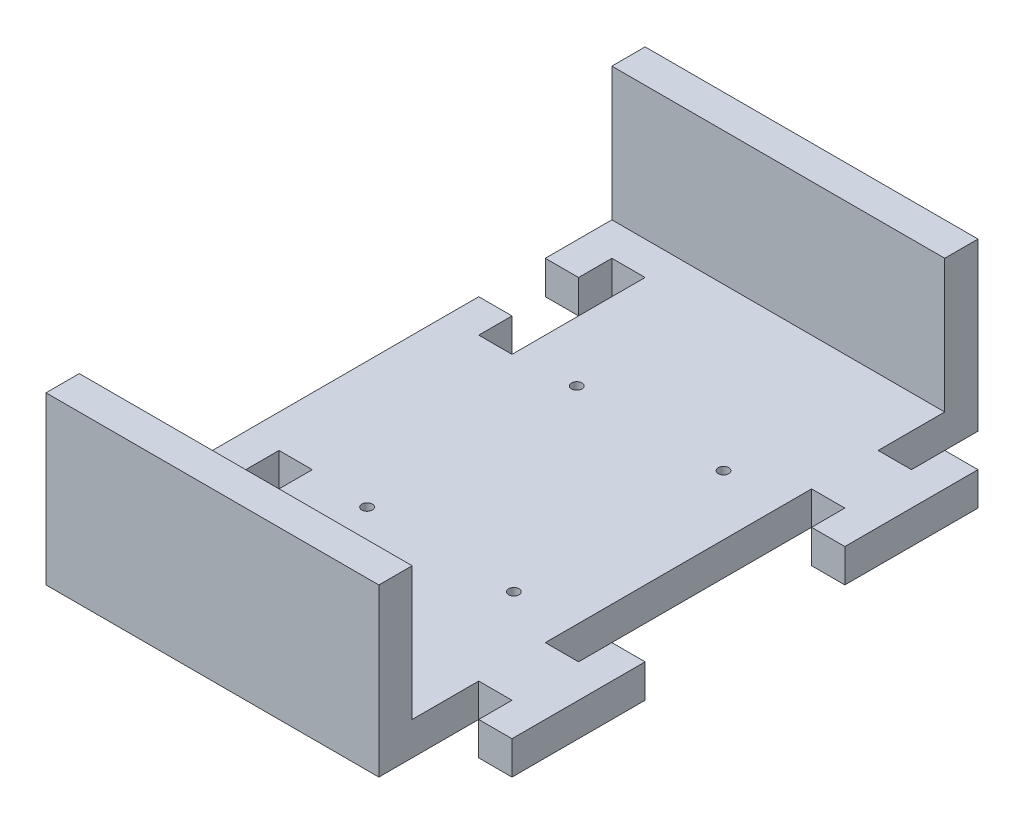
SolidWorks part; units mm, degrees
ref_plane "Front Plane" through (0, 0, 0) normal (0, 0, 1) x (1, 0, 0)
ref_plane "Top Plane" through (0, 0, 0) normal (0, 1, 0) x (1, 0, 0)
ref_plane "Right Plane" through (0, 0, 0) normal (1, 0, 0) x (0, 0, -1)
sketch "Sketch1" plane through (0, 0, 0) normal (0, 1, 0) x (1, 0, 0)
  line L1 (-38.1, -57.15) -> (25.4, -57.15)
  line L2 (-38.1, -57.15) -> (-38.1, 57.15)
  line L3 (-38.1, 57.15) -> (25.4, 57.15)
  line L4 (25.4, -57.15) -> (25.4, 57.15)
  line L5 (-38.1, -57.15) -> (25.4, 57.15) construction
  line L6 (-38.1, 57.15) -> (25.4, -57.15) construction
  point P0 (-6.35, 0)
  point P6 (0, 0)
  dimension "D1" = 63.5
  dimension "D2" = 114.3
  dimension "D3" = 6.35
extrude "Boss-Extrude1" add sketch "Sketch1" along normal blind 6.35
sketch "Sketch2" plane through (0, 6.35, 0) normal (0, 1, 0) x (1, 0, 0)
  line L1 (-14, -20) -> (14, -20) construction
  line L2 (-14, -20) -> (-14, 20) construction
  line L3 (-14, 20) -> (14, 20) construction
  line L4 (14, -20) -> (14, 20) construction
  line L5 (-14, -20) -> (14, 20) construction
  line L6 (-14, 20) -> (14, -20) construction
  circle A0 centre (-14, 20) radius 1
  circle A1 centre (14, 20) radius 1
  circle A2 centre (14, -20) radius 1
  circle A3 centre (-14, -20) radius 1
  point P0 (0, 0)
  dimension "D3" = 2
  dimension "D1" = 28
  dimension "D2" = 40
extrude "Cut-Extrude1" cut sketch "Sketch2" against normal through all
sketch "Sketch3" plane through (0, 6.35, 0) normal (0, 1, 0) x (1, 0, 0)
  line L0 (25.4, -57.15) -> (25.4, 57.15) construction
  line L1 (-38.1, 57.15) -> (25.4, 57.15)
  line L2 (-38.1, 57.15) -> (-38.1, 50.8)
  line L3 (-38.1, 50.8) -> (25.4, 50.8)
  line L4 (25.4, 57.15) -> (25.4, 50.8)
  line L6 (-38.1, -57.15) -> (25.4, -57.15)
  line L7 (-38.1, -57.15) -> (-38.1, -50.8)
  line L8 (-38.1, -50.8) -> (25.4, -50.8)
  line L9 (25.4, -57.15) -> (25.4, -50.8)
  dimension "D1" = 6.35
extrude "Boss-Extrude2" add sketch "Sketch3" along normal blind 25.4
sketch "Sketch6" plane through (0, 6.35, 0) normal (0, 1, 0) x (1, 0, 0)
  line L0 (25.4, -50.8) -> (25.4, 50.8) construction
  line L1 (25.4, 38.1) -> (31.75, 38.1)
  line L2 (25.4, 38.1) -> (25.4, 25.4)
  line L3 (25.4, 25.4) -> (31.75, 25.4)
  line L5 (25.4, 57.15) -> (-38.1, 57.15) construction
  line L6 (31.75, 44.45) -> (38.1, 44.45)
  line L7 (31.75, 44.45) -> (31.75, 38.1)
  line L8 (31.75, 19.05) -> (38.1, 19.05)
  line L9 (38.1, 44.45) -> (38.1, 19.05)
  line L10 (31.75, 25.4) -> (31.75, 19.05)
  point P10 (38.1, 31.75)
  point P11 (25.4, 31.75)
  dimension "D1" = 6.35
  dimension "D2" = 12.7
  dimension "D3" = 25.4
  dimension "D4" = 6.35
  dimension "D5" = 25.4
extrude "Boss-Extrude3" add sketch "Sketch6" against normal up to surface (6.35 mm away) up to face at (-14, 0, 21)
sketch "Sketch7" plane through (0, 6.35, 0) normal (0, 1, 0) x (1, 0, 0)
  line L0 (-38.1, 50.8) -> (-38.1, -50.8) construction
  line L1 (-38.1, 38.1) -> (-31.75, 38.1)
  line L2 (-38.1, 38.1) -> (-38.1, 25.4)
  line L3 (-38.1, 25.4) -> (-31.75, 25.4)
  line L5 (-31.75, 25.4) -> (-31.75, 19.05)
  line L6 (-25.4, 44.45) -> (-31.75, 44.45)
  line L7 (-25.4, 44.45) -> (-25.4, 19.05)
  line L8 (-25.4, 19.05) -> (-31.75, 19.05)
  line L9 (-31.75, 44.45) -> (-31.75, 38.1)
  line L10 (31.75, 38.1) -> (25.4, 38.1) construction
  line L11 (38.1, 44.45) -> (31.75, 44.45) construction
  line L12 (31.75, 44.45) -> (31.75, 38.1) construction
  line L13 (38.1, 19.05) -> (38.1, 44.45) construction
extrude "Cut-Extrude2" cut sketch "Sketch7" against normal through all
mirror "Mirror1" about plane through (0, 0, 0) normal (0, 0, 1) of "Boss-Extrude3", "Cut-Extrude2"
